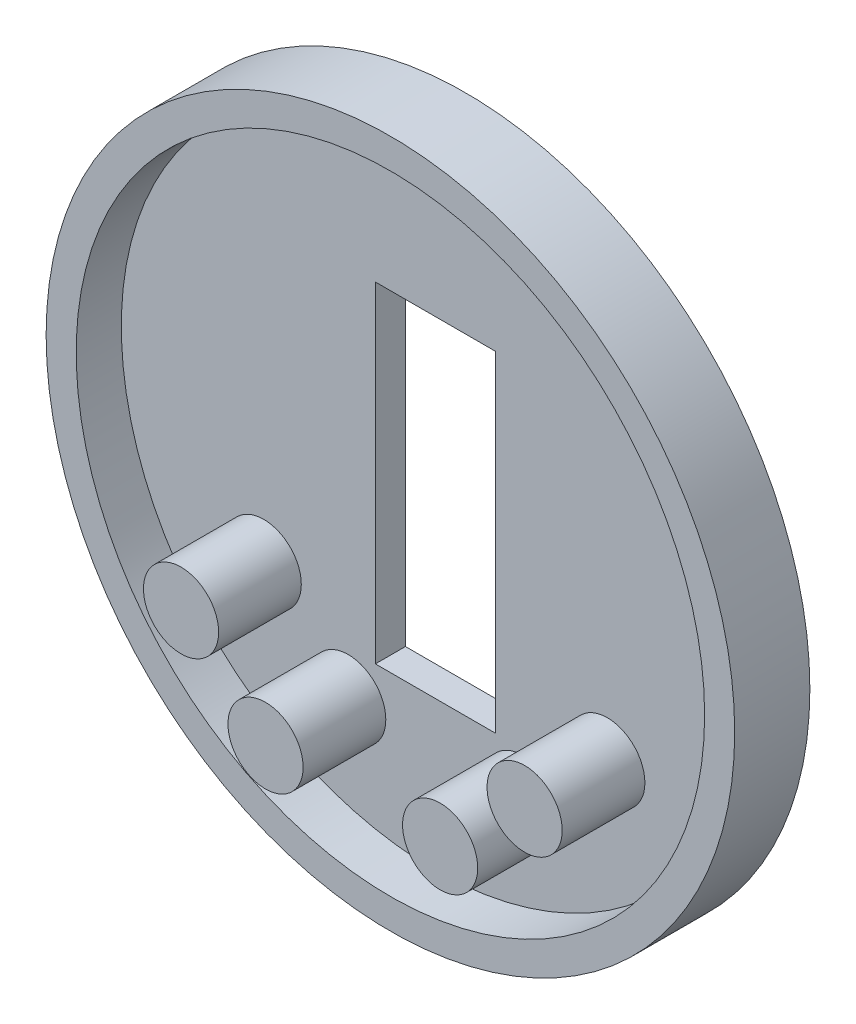
SolidWorks part; units mm, degrees
ref_plane "Ebene vorne" through (0, 0, 0) normal (0, 0, 1) x (1, 0, 0)
ref_plane "Ebene oben" through (0, 0, 0) normal (0, 1, 0) x (1, 0, 0)
ref_plane "Ebene rechts" through (0, 0, 0) normal (1, 0, 0) x (0, 0, -1)
sketch "Skizze1" plane through (0, 0, 0) normal (0, 1, 0) x (1, 0, 0)
  line L0 (0, 0) -> (22.902, 0)
  line L1 (22.902, 0) -> (22.902, -5)
  line L2 (22.902, -5) -> (20.902, -5)
  line L3 (20.902, -5) -> (20.902, -2)
  line L4 (20.902, -2) -> (0, -2)
  line L5 (0, -2) -> (0, 0)
revolve "Rotation2" add sketch "Skizze1" angle 360 about L5
sketch "Skizze2" plane through (0, 0, 0) normal (0, 0, -1) x (-1, 0, 0)
  line L0 (0, 0) -> (4, 0)
  line L4 (4, 11) -> (-4, 11)
  line L5 (-4, 11) -> (-4, -11)
  line L6 (4, 11) -> (4, -11)
  line L7 (4, -11) -> (-4, -11)
extrude "Schnitt-Linear austragen1" cut sketch "Skizze2" against normal blind 10 contours L7 L6 L4 L5 region at (-3.7659, 5.5, 0)
sketch "Skizze3" plane through (0, 0, 0) normal (0, 0, 1) x (1, 0, 0)
  circle A0 centre (-5.8065, -13.863) radius 2.5
  circle A1 centre (5.8065, -13.863) radius 2.5
  circle A2 centre (-11.4275, -8.885) radius 2.5
  circle A3 centre (11.4275, -8.885) radius 2.5
extrude "Aufsatz-Linear austragen1" add sketch "Skizze3" along normal blind 7.5 contours A3
extrude "Aufsatz-Linear austragen2" add sketch "Skizze3<5>" along normal blind 7.5 contours A1 region at (5.8065, -13.863, 0)
sketch "Skizze3<5>" plane through (0, 0, 0) normal (0, 0, 1) x (1, 0, 0) same geometry as "Skizze3"
extrude "Aufsatz-Linear austragen3" add sketch "Skizze3<6>" along normal blind 7.5 contours A0 region at (-5.8065, -13.863, 0)
sketch "Skizze3<6>" plane through (0, 0, 0) normal (0, 0, 1) x (1, 0, 0) same geometry as "Skizze3"
extrude "Aufsatz-Linear austragen4" add sketch "Skizze3<7>" along normal blind 7.5 contours A2
sketch "Skizze3<7>" plane through (0, 0, 0) normal (0, 0, 1) x (1, 0, 0) same geometry as "Skizze3"
